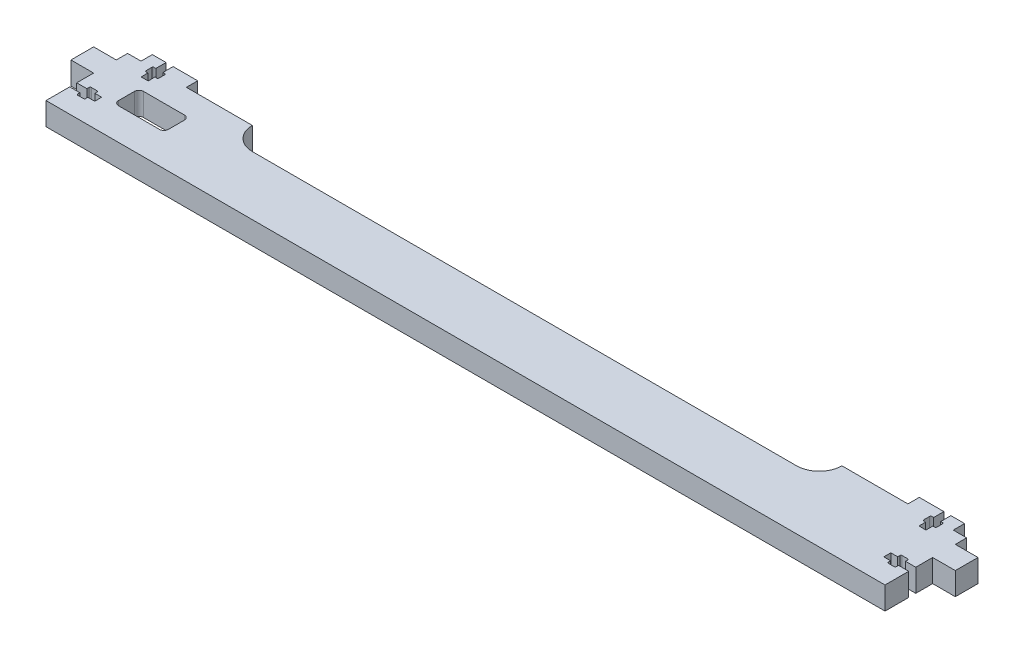
SolidWorks part; units mm, degrees
ref_plane "Front Plane" through (0, 0, 0) normal (0, 0, 1) x (1, 0, 0)
ref_plane "Top Plane" through (0, 0, 0) normal (0, 1, 0) x (1, 0, 0)
ref_plane "Right Plane" through (0, 0, 0) normal (1, 0, 0) x (0, 0, -1)
sketch "Sketch1" plane through (0, 0, 0) normal (0, 1, 0) x (1, 0, 0)
  line L0 (0, 18) -> (0, -18) construction
  line L1 (-185, 18) -> (0, 18)
  line L2 (-185, 18) -> (-185, 13)
  line L3 (-185, -18) -> (0, -18)
  line L4 (0, 18) -> (0, -18)
  line L5 (-185, 18) -> (0, 0) construction
  line L6 (-185, -18) -> (0, 0) construction
  line L7 (-185, 13) -> (-195, 13)
  line L8 (-195, 13) -> (-195, 3)
  line L9 (-195, 3) -> (-185, 3)
  line L10 (-185, 3) -> (-185, -18)
  point P0 (0, 0)
  dimension "D6" = 10
  dimension "D7" = 10
  dimension "D1" = 185
  dimension "D2" = 36
  dimension "D4" = 5
  dimension "D9" = 18
extrude "MainShape" add sketch "Sketch1" along normal blind 10 contours L2 L7 L8 L9 region at (-93.9423, 0, -0.1183)
sketch "Sketch15" plane through (0, 10, 0) normal (0, 1, 0) x (1, 0, 0)
  line L0 (-185, 18) -> (0, 18) construction
  line L1 (-159.1, 23) -> (-179.1, 23)
  line L2 (-159.1, 23) -> (-159.1, 13)
  line L3 (-159.1, 13) -> (-179.1, 13)
  line L4 (-179.1, 23) -> (-179.1, 13)
  line L5 (-159.1, 23) -> (-179.1, 13) construction
  line L6 (-159.1, 13) -> (-179.1, 23) construction
  line L7 (-185, 18) -> (-185, 13) construction
  point P0 (-169.1, 18)
  dimension "D1" = 20
  dimension "D2" = 5
  dimension "D3" = 15.9
extrude "Boss-Extrude4" add sketch "Sketch15" against normal through all
sketch "Sketch2" plane through (0, 10, 0) normal (0, 1, 0) x (1, 0, 0)
  line L0 (-171.5, 23) -> (-171.5, 12) construction
  line L2 (-173.05, 23) -> (-173.05, 18.5)
  line L3 (-173.05, 18.5) -> (-173.85, 18.5)
  line L4 (-174.35, 18) -> (-174.35, 15.5)
  line L5 (-173.85, 15) -> (-173.05, 15)
  line L6 (-173.05, 15) -> (-173.05, 12)
  line L7 (-173.05, 12) -> (-169.95, 12)
  line L8 (-185, 18) -> (-185, 13) construction
  line L9 (-173.05, 23) -> (-169.95, 23)
  line L10 (-169.95, 15) -> (-169.95, 12)
  line L11 (-169.15, 15) -> (-169.95, 15)
  line L12 (-168.65, 18) -> (-168.65, 15.5)
  line L13 (-169.95, 18.5) -> (-169.15, 18.5)
  line L14 (-169.95, 23) -> (-169.95, 18.5)
  line L16 (-185, -6) -> (-174, -6) construction
  line L17 (-159.1, 23) -> (-179.1, 23) construction
  line L50 (-185, 3) -> (-185, -18) construction
  line L51 (-174, -7.55) -> (-174, -4.45)
  line L52 (-174, -4.45) -> (-177, -4.45)
  line L53 (-177, -4.45) -> (-177, -3.5)
  line L54 (-177.5, -3) -> (-180, -3)
  line L55 (-180.5, -3.5) -> (-180.5, -4.45)
  line L56 (-180.5, -4.45) -> (-185, -4.45)
  line L57 (-185, -4.45) -> (-185, -7.55)
  line L58 (-195, 13) -> (-195, 3) construction
  line L59 (-180.5, -7.55) -> (-185, -7.55)
  line L60 (-180.5, -8.5) -> (-180.5, -7.55)
  line L61 (-177.5, -9) -> (-180, -9)
  line L62 (-177, -7.55) -> (-177, -8.5)
  line L63 (-174, -7.55) -> (-177, -7.55)
  arc A0 (-174.35, 15.5) -> (-173.85, 15) centre (-173.85, 15.5) ccw
  arc A1 (-173.85, 18.5) -> (-174.35, 18) centre (-173.85, 18) ccw
  arc A2 (-169.15, 18.5) -> (-168.65, 18) centre (-169.15, 18) cw
  arc A3 (-168.65, 15.5) -> (-169.15, 15) centre (-169.15, 15.5) cw
  arc A16 (-177, -3.5) -> (-177.5, -3) centre (-177.5, -3.5) ccw
  arc A17 (-180, -3) -> (-180.5, -3.5) centre (-180, -3.5) ccw
  arc A18 (-180, -9) -> (-180.5, -8.5) centre (-180, -8.5) cw
  arc A19 (-177, -8.5) -> (-177.5, -9) centre (-177.5, -8.5) cw
  point P14 (-174.35, 15)
  point P17 (-174.35, 18.5)
  point P28 (-168.65, 18.5)
  point P29 (-168.65, 15)
  point P34 (-195, 8)
  point P45 (-177, -3)
  point P48 (-180.5, -3)
  dimension "D8" = 0.5
  dimension "D16" = 0.5
  dimension "D1" = 11
  dimension "D2" = 1.55
  dimension "D3" = 1.55
  dimension "D5" = 2.85
  dimension "D6" = 3.5
  dimension "D7" = 13.5
  dimension "D9" = 11
  dimension "D10" = 8
  dimension "D11" = 3.5
  dimension "D12" = 3
  dimension "D13" = 1.55
  dimension "D14" = 1.55
  dimension "D15" = 14
  dimension "D4" = 8
extrude "ScrewSlots" cut sketch "Sketch2" against normal through all
mirror "Mirror1" about plane through (0, 0, 0) normal (1, 0, 0) of "Boss-Extrude4", "ScrewSlots", "MainShape"
sketch "Sketch6" plane through (0, 10, 0) normal (0, 1, 0) x (1, 0, 0)
  line L0 (0, -18) -> (0, -48) construction
  line L2 (-185, -18) -> (185, -18) construction
  line L3 (90, -48) -> (-90, -48)
  line L4 (-90, -48) -> (-120, -18)
  line L5 (90, -48) -> (120, -18)
  line L6 (-120, -18) -> (120, -18)
  dimension "D1" = 135
  dimension "D2" = 30
  dimension "D3" = 90
extrude "Boss-Extrude1" [suppressed] add sketch "Sketch6" against normal through all
sketch "Sketch8" plane through (0, 10, 0) normal (0, 1, 0) x (1, 0, 0)
  line L0 (-71.5, 4.8833) -> (-77.5, 4.8833) construction
  line L1 (-77, -1.6167) -> (-72, -1.6167)
  line L2 (-78, -0.6167) -> (-78, 4.3833)
  line L3 (-77, 5.3833) -> (-72, 5.3833)
  line L4 (-71, -0.6167) -> (-71, 4.3833)
  line L5 (-78, -1.6167) -> (-71, 5.3833) construction
  line L6 (-78, 5.3833) -> (-71, -1.6167) construction
  line L7 (-71.5, -1.1167) -> (-71.5, 4.8833) construction
  circle A0 centre (-74.5, -34.7667) radius 6.5
  circle A1 centre (-74.5, -15.8167) radius 5.5
  arc A2 (-77, -1.6167) -> (-78, -0.6167) centre (-77, -0.6167) cw
  circle A3 centre (-74.5, -34.7667) radius 6 construction
  circle A4 centre (-74.5, -15.8167) radius 3.5 construction
  arc A5 (-72, -1.6167) -> (-71, -0.6167) centre (-72, -0.6167) ccw
  arc A6 (-72, 5.3833) -> (-71, 4.3833) centre (-72, 4.3833) cw
  arc A7 (-78, 4.3833) -> (-77, 5.3833) centre (-77, 4.3833) cw
  point P6 (-74.5, 1.8833)
  dimension "D1" = 0.5
  dimension "D2" = 2
  dimension "D3" = 0.5
  dimension "D5" = 1
  dimension "D4" = 0.5
extrude "Cut-Extrude2" [suppressed] cut sketch "Sketch8" against normal through all
sketch "Sketch7" plane through (0, 10, 0) normal (0, 1, 0) x (1, 0, 0)
  circle A0 centre (60.5, -43.0167) radius 1.45
  circle A1 centre (-84.5, -43.0167) radius 1.45
  circle A2 centre (-84.5, 6.4833) radius 1.45
  circle A3 centre (60.5, 6.4833) radius 1.45
  dimension "D1" = 2.9
  dimension "D2" = 2.9
  dimension "D3" = 2.9
  dimension "D4" = 2.9
extrude "Cut-Extrude1" [suppressed] cut sketch "Sketch7" against normal through all
sketch "Sketch9" plane through (0, 10, 0) normal (0, 1, 0) x (1, 0, 0)
  line L0 (0, 7.2333) -> (0, -32.7667) construction
  line L1 (48.5, 7.2333) -> (-48.5, 7.2333) construction
  line L2 (-48.5, -32.7667) -> (48.5, -32.7667) construction
  line L3 (-48.5, -12.7667) -> (48.5, -12.7667) construction
  line L4 (-48.5, 7.2333) -> (-48.5, -32.7667) construction
  line L5 (48.5, -32.7667) -> (48.5, 7.2333) construction
  line L7 (-49, -33.2667) -> (49, -33.2667)
  line L8 (-49, -33.2667) -> (-49, 7.7333)
  line L9 (-49, 7.7333) -> (49, 7.7333)
  line L10 (49, -33.2667) -> (49, 7.7333)
  line L11 (-49, -33.2667) -> (49, 7.7333) construction
  line L12 (-49, 7.7333) -> (49, -33.2667) construction
  point P12 (0, -12.7667)
  dimension "D1" = 0.5
  dimension "D2" = 0.5
extrude "Cut-Extrude3" [suppressed] cut sketch "Sketch9" against normal through all and the other way through all
sketch "Sketch10" plane through (0, 10, 0) normal (0, 1, 0) x (1, 0, 0)
  line L0 (20, -39.2667) -> (20, -40.7667) construction
  line L1 (40, -39.2667) -> (0, -39.2667) construction
  line L2 (0, -40.7667) -> (40, -40.7667) construction
  line L3 (0, -40.0167) -> (40, -40.0167) construction
  line L4 (0, -39.2667) -> (0, -40.7667) construction
  line L5 (40, -40.7667) -> (40, -39.2667) construction
  line L7 (-0.2, -40.9667) -> (40.2, -40.9667)
  line L8 (-0.2, -40.9667) -> (-0.2, -39.0667)
  line L9 (-0.2, -39.0667) -> (40.2, -39.0667)
  line L10 (40.2, -40.9667) -> (40.2, -39.0667)
  line L11 (-0.2, -40.9667) -> (40.2, -39.0667) construction
  line L12 (-0.2, -39.0667) -> (40.2, -40.9667) construction
  point P12 (20, -40.0167)
  dimension "D1" = 0.2
  dimension "D2" = 0.2
extrude "Cut-Extrude4" [suppressed] cut sketch "Sketch10" against normal through all
sketch "Sketch12" [suppressed] plane through (0, 0, 0) normal (0, -1, 0) x (-1, 0, 0)
  line L1 (81.4, -9.8167) -> (67.6, -9.8167)
  line L2 (81.4, -9.8167) -> (81.4, -21.8167)
  line L3 (81.4, -21.8167) -> (67.6, -21.8167)
  line L4 (67.6, -9.8167) -> (67.6, -21.8167)
  line L5 (81.4, -9.8167) -> (67.6, -21.8167) construction
  line L6 (81.4, -21.8167) -> (67.6, -9.8167) construction
  point P0 (74.5, -15.8167)
  dimension "D1" = 13.8
  dimension "D2" = 12
extrude "PotentiometerAdjustment" [suppressed] cut sketch "Sketch12" against normal through all
sketch "Sketch11" plane through (0, 0, 0) normal (0, -1, 0) x (1, 0, 0)
  line L1 (-149, -7) -> (-167, -7)
  line L2 (-147, -5) -> (-147, 2)
  line L3 (-149, 4) -> (-167, 4)
  line L4 (-169, -5) -> (-169, 2)
  line L5 (-147, -7) -> (-169, 4) construction
  line L6 (-147, 4) -> (-169, -7) construction
  line L7 (173.05, -12) -> (169.95, -12) construction
  line L8 (-174, 7.55) -> (-174, 4.45) construction
  arc A0 (-147, 2) -> (-149, 4) centre (-149, 2) ccw
  arc A1 (-167, 4) -> (-169, 2) centre (-167, 2) ccw
  arc A2 (-167, -7) -> (-169, -5) centre (-167, -5) cw
  arc A3 (-149, -7) -> (-147, -5) centre (-149, -5) ccw
  point P0 (-158, -1.5)
  dimension "D3" = 2
  dimension "D1" = 22
  dimension "D2" = 11
  dimension "D4" = 5
  dimension "D5" = 5
extrude "LCDCableCutout" cut sketch "Sketch11" against normal through all
sketch "Sketch13" plane through (0, 10, 0) normal (0, 1, 0) x (1, 0, 0)
  line L0 (0, 18) -> (0, -18) construction
  line L1 (-169.95, 18) -> (169.95, 18) construction
  line L2 (-185, -18) -> (185, -18) construction
  line L3 (120, 18) -> (-120, 18) construction
  line L4 (120, 8) -> (-120, 8)
  line L5 (120, 28) -> (-120, 28)
  arc A0 (120, 8) -> (120, 28) centre (120, 18) ccw
  arc A1 (-120, 28) -> (-120, 8) centre (-120, 18) ccw
  point P8 (0, 18)
  dimension "D2" = 120
  dimension "D1" = 10
extrude "Cut-Extrude5" cut sketch "Sketch13" against normal through all
sketch "Sketch14" plane through (0, 10, 0) normal (0, 1, 0) x (1, 0, 0)
  line L1 (-169.95, 18) -> (169.95, 18) construction
  line L3 (-156.5, 18) -> (-156.5, 28) construction
  line L4 (-161.5, 18) -> (-151.5, 18)
  line L5 (-161.5, 18) -> (-161.5, 28)
  line L6 (-161.5, 28) -> (-151.5, 28)
  line L7 (-151.5, 18) -> (-151.5, 28)
  line L8 (-173.05, 12) -> (-169.95, 12) construction
  line L9 (154, 18) -> (154, 28) construction
  line L10 (149, 18) -> (149, 28)
  line L11 (159, 28) -> (149, 28)
  line L12 (159, 18) -> (159, 28)
  line L13 (159, 18) -> (149, 18)
  point P12 (-171.5, 12)
  dimension "D1" = 10
  dimension "D2" = 10
  dimension "D3" = 15
extrude "Boss-Extrude3" [suppressed] add sketch "Sketch14" against normal through all
equation "\"Y-ROD-SPACING\"=75"
equation "\"Y-BED-OFFSET\"=2"
equation "\"Y-BED-ROD-INSET\"=3.5"
equation "\"T-SLOT-NUT-FILLET-RADIUS\"=0.5"
equation "\"T-SLOT-SCREW-SHAFT-RADIUS\"=1.55"
equation "\"T-SLOT-SCREW-SHAFT-CUTOUT-LENGTH\"=11"
equation "\"T-SLOT-NUT-DEPTH\"=3.5"
equation "\"T-SLOT-NUT-WIDTH\"=2.85"
equation "\"T-SLOT-NUT-END-DISTANCE\"=8"
equation "\"ACRYLIC-TAB-CUTOUT-SIZE\"=\"ACRYLIC-THICKNESS\"+\"ACRYLIC-TAB-TOLERANCE\"*2"
equation "\"ACRYLIC-M3-HOLE\"=2.9"
equation "\"SMOOTHROD-CAP-SCREW-DISTANCE\"=20"
equation "\"D2@Sketch2\"=\"T-SLOT-SCREW-SHAFT-RADIUS\""
equation "\"D1@Sketch2\"=\"T-SLOT-SCREW-SHAFT-CUTOUT-LENGTH\""
equation "\"D6@Sketch2\"=\"T-SLOT-NUT-DEPTH\""
equation "\"D5@Sketch2\"=\"T-SLOT-NUT-WIDTH\""
equation "\"D3@Sketch2\"=\"T-SLOT-SCREW-SHAFT-RADIUS\""
equation "\"D8@Sketch2\"=\"T-SLOT-NUT-FILLET-RADIUS\""
equation "\"D4@Sketch2\"=\"T-SLOT-NUT-END-DISTANCE\""
equation "\"D11@Sketch2\"=\"T-SLOT-NUT-DEPTH\""
equation "\"D10@Sketch2\"=\"T-SLOT-NUT-END-DISTANCE\""
equation "\"D13@Sketch2\"=\"T-SLOT-SCREW-SHAFT-RADIUS\""
equation "\"D14@Sketch2\"=\"T-SLOT-SCREW-SHAFT-RADIUS\""
equation "\"D16@Sketch2\"=\"T-SLOT-NUT-FILLET-RADIUS\""
equation "\"D9@Sketch2\"=\"T-SLOT-SCREW-SHAFT-CUTOUT-LENGTH\""
equation "\"ACRYLIC-TAB-WIDTH\"=\"ACRYLIC-THICKNESS\""
equation "\"D6@Sketch1\"=\"ACRYLIC-TAB-WIDTH\""
equation "\"D7@Sketch1\"=\"ACRYLIC-TAB-WIDTH\""
equation "\"FRAME-WIDTH-INNER\"=370"
equation "\"D1@Sketch1\"=\"FRAME-WIDTH-INNER\"/2"
equation "\"X-ROD-SPACING\"=45"
equation "\"Z-ROD-SPACING\"=17.5"
equation "\"ACRYLIC-THICKNESS\"=10"
equation "\"ACRYLIC-THICKNESS2\"=4.5"
equation "\"NEMA17-HOLE-SPACING\"=31"
equation "\"NEMA17-CENTRAL-CUTOUT\"=22.5"
equation "\"Z-BRACKET-REACH\"=57"
equation "\"TOP-BRACKET-SPACING\"=40"
equation "\"SMOOTHROD-X-LENGTH\"=350"
equation "\"SMOOTHROD-Y-LENGTH\"=350"
equation "\"SMOOTHROD-Z-LENGTH\"=350"
equation "\"SMOOTHROD-TIGHTENING-HEADROOM\"=.25"
equation "\"LEADSCREW-Z-LENGTH\"=300"
equation "\"SCREW-LENGTH-FRAME\"=\"ACRYLIC-THICKNESS\" + 10"
equation "\"SCREW-HEAD-RADIUS\"=6"
equation "\"PRINTED-X-SMOOTHROD-DIAMETER\"=8.8"
equation "\"PRINTED-X-SMOOTHROD-CUTOUT\"=10"
equation "\"PRINTED-X-BASE-HEIGHT\"=10"
equation "\"PRINTED-LM8UU-CUTOUT-SIZE\"=15.5"
equation "\"PRINTED-LM8UU-CUTOUT-LENGTH\"=24.5"
equation "\"PRINTED-X-IDLER-HEIGHT\"=16"
equation "\"PSU-MOUNTING-WIDTH\"=95"
equation "\"PSU-MOUNTING-HEIGHT\"=177"
equation "\"D1@MainShape\"=\"ACRYLIC-THICKNESS\""
equation "\"Y-BELT-TO-ROD-DISTANCE\"=20"
equation "\"SPOOL-HOLDER-ROD-SPACING\"=150"
equation "\"Z-ROD-INSET\"=13.5"
equation "\"D7@Sketch2\"=\"Z-ROD-INSET\""
equation "\"D1@Sketch7\"=\"ACRYLIC-M3-HOLE\""
equation "\"D2@Sketch7\"=\"ACRYLIC-M3-HOLE\""
equation "\"D3@Sketch7\"=\"ACRYLIC-M3-HOLE\""
equation "\"D4@Sketch7\"=\"ACRYLIC-M3-HOLE\""
equation "\"Y-BED-SCREW-SPACING\"=209"
equation "\"Y-BED-SCREW-CUTOUT-SLOT-HEIGHT\"=2.5"
equation "\"ACRYLIC-TAB-TOLERANCE\"=-.05"
equation "\"SCREW-LENGTH-MOTOR\"=\"ACRYLIC-THICKNESS\" + 5"
equation "\"SCREW-LENGTH-EXTRUDER\"=28"
equation "\"PRINTED-M3-HOLE\"=3.5"
equation "\"PRINTED-M3-NUT-AF\"=6.25"
equation "\"ACRYLIC-X-CARRIAGE-WIDTH\"=55"
equation "\"ACRYLIC-X-CARRIAGE-HEIGHT\"=75"
equation "\"ACRYLIC-X-CARRIAGE-LM8UU-CUTOUT-WIDTH\"=24.25"
equation "\"ACRYLIC-X-CARRIAGE-LM8UU-CUTOUT-HEIGHT\"=11.0"
equation "\"ACRYLIC-X-CARRIAGE-SCREW-SPACING-X\"=15"
equation "\"ACRYLIC-X-CARRIAGE-SCREW-SPACING-Y\"=33"
equation "\"ACRYLIC-X-CARRIAGE-CENTER-TAB-SPACING\"=14"
equation "\"ACRYLIC-X-CARRIAGE-EXTRUDER-OFFSET\"=26"
equation "\"ACRYLIC-X-CARRIAGE-EXTRUDER-ANGLE\"=90"
equation "\"ACRYLIC-X-CARRIAGE-EXTRUDER-SHELF-DEPTH\"=\"ACRYLIC-X-CARRIAGE-EXTRUDER-OFFSET\" + 28"
equation "\"ACRYLIC-X-CARRIAGE-EXTRUDER-BRACE-SPACING\"=23"
equation "\"ACRYLIC-X-CARRIAGE-EXTRUDER-BRACE-TAB-OFFSET\"=20"
equation "\"ACRYLIC-X-CARRIAGE-EXTRUDER-BRACE-HEIGHT\"=35"
equation "\"ACRYLIC-X-CARRIAGE-EXTRUDER-BRACE-SCREW-SPACING\"=22"
equation "\"ACRYLIC-X-CARRIAGE-DUAL-WIDTH-MULTIPLIER\"=1.65"
equation "\"ACRYLIC-X-CARRIAGE-DUAL-HOTEND-SPACING\"=42"
equation "\"ACRYLIC-X-CARRIAGE-DUAL-WIDTH\"=75"
equation "\"ACRYLIC-X-CARRIAGE-DUAL-HOTEND-SEPARATION\"=36"
equation "\"ACRYLIC-X-CARRIAGE-DUAL-MOUNT-PLATE-DEPTH\"=75"
equation "\"ACRYLIC-X-CARRIAGE-DUAL-MOUNT-BRACE-WIDTH\"=33"
equation "\"ACRYLIC-X-CARRIAGE-DUAL-MOUNT-SCREW-WIDTH\"=40"
equation "\"BLOWER-FAN-WIDTH\"=15"
equation "\"D1@Sketch14\"=\"ACRYLIC-TAB-WIDTH\""
equation "\"D2@Sketch14\"=\"ACRYLIC-THICKNESS\""
equation "\"D3@Sketch15\"=\"Z-ROD-INSET\"+2.4"
